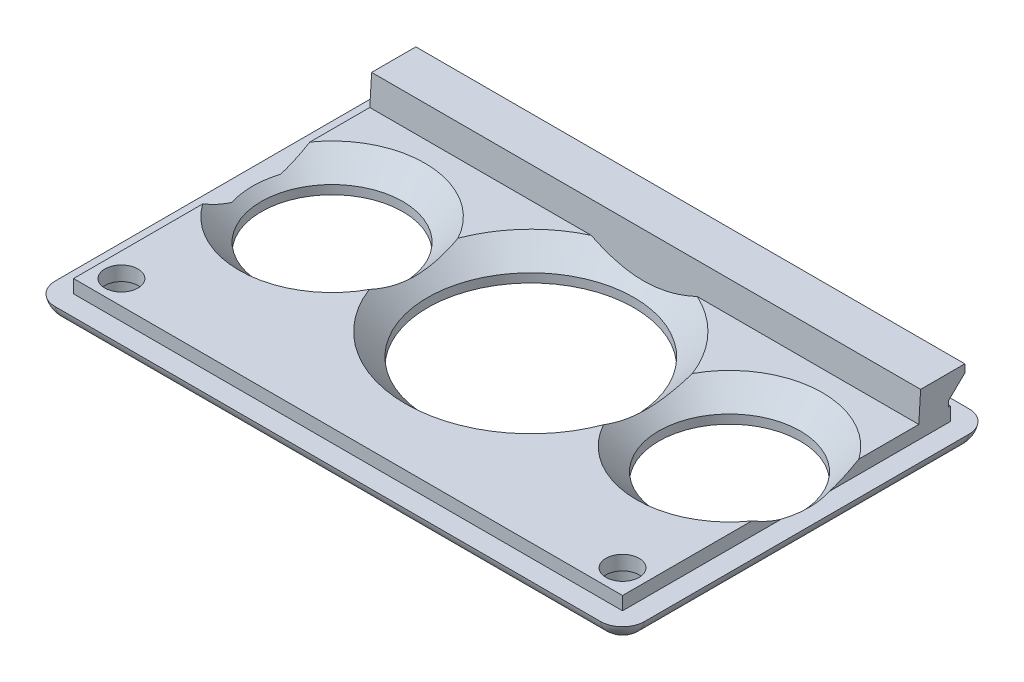
SolidWorks part; units mm, degrees
ref_plane "Front Plane" through (0, 0, 0) normal (0, 0, 1) x (1, 0, 0)
ref_plane "Top Plane" through (0, 0, 0) normal (0, 1, 0) x (1, 0, 0)
ref_plane "Right Plane" through (0, 0, 0) normal (1, 0, 0) x (0, 0, -1)
sketch "Sketch1" plane through (0, 0, 0) normal (0, 1, 0) x (1, 0, 0)
  line L1 (-1.2463, 1.173) -> (78.7537, 1.173)
  line L2 (-1.2463, 1.173) -> (-1.2463, 51.173)
  line L3 (-1.2463, 51.173) -> (78.7537, 51.173)
  line L4 (78.7537, 1.173) -> (78.7537, 51.173)
  dimension "D1" = 50
  dimension "D2" = 80
extrude "Boss-Extrude1" add sketch "Sketch1" along normal blind 2.4
sketch "Sketch2" plane through (0, 2.4, 0) normal (0, 1, 0) x (1, 0, 0)
  line L0 (38.7537, 51.173) -> (38.7537, 1.173) construction
  line L1 (78.7537, 51.173) -> (-1.2463, 51.173) construction
  line L2 (-1.2463, 1.173) -> (78.7537, 1.173) construction
  line L3 (-1.2463, 51.173) -> (-1.2463, 1.173) construction
  line L4 (1.5037, 48.423) -> (76.0037, 48.423)
  line L5 (1.5037, 48.423) -> (1.5037, 3.923)
  line L6 (1.5037, 3.923) -> (76.0037, 3.923)
  line L7 (76.0037, 48.423) -> (76.0037, 3.923)
  line L8 (1.5037, 48.423) -> (76.0037, 3.923) construction
  line L9 (1.5037, 3.923) -> (76.0037, 48.423) construction
  point P6 (38.7537, 26.173)
  dimension "D1" = 2.75
  dimension "D2" = 2.75
extrude "Boss-Extrude2" add sketch "Sketch2" along normal blind 1.8
sketch "Sketch3" [suppressed] plane through (0, 0, 0) normal (0, -1, 0) x (-1, 0, 0)
  line L1 (-74.0007, 57.8979) -> (-74.348, 7.8991) construction
  line L2 (-74.348, 7.8991) -> (0.6502, 7.3782) construction
  line L3 (0.6502, 7.3782) -> (0.9975, 57.377) construction
  line L4 (0.9975, 57.377) -> (-74.0007, 57.8979) construction
  circle A0 centre (-61.0257, 35.0904) radius 9.305
  circle A1 centre (-36.6576, 35.188) radius 13.2617
  circle A2 centre (-12.0957, 35.0904) radius 9.305
  circle A3 centre (-67.6316, 45.7049) radius 3.1
  circle A4 centre (-18.7016, 45.7049) radius 3.1
  circle A5 centre (-68.3065, 13.8573) radius 1.75
  circle A6 centre (-5.3158, 13.4277) radius 1.75
sketch "Sketch4" plane through (0, 0, 0) normal (0, -1, 0) x (-1, 0, 0)
  line L0 (-78.7537, 55.2723) -> (-78.7537, 28.723) construction
  line L1 (1.2463, 1.173) -> (-78.7537, 1.173) construction
  line L2 (-65.7187, 28.723) -> (-38.7537, 28.723) construction
  line L3 (-38.7537, 28.723) -> (-11.7887, 28.723) construction
  line L4 (-65.7187, 28.723) -> (-78.7537, 28.723) construction
  line L5 (-4.7537, 7.173) -> (-72.7537, 7.173) construction
  line L6 (-72.7537, 7.173) -> (-73.7537, 7.173) construction
  line L7 (-73.7537, 7.173) -> (-72.7537, 7.173) construction
  line L8 (-72.7537, 7.173) -> (-72.7537, 4.923) construction
  line L9 (-72.7537, 4.923) -> (-72.7537, 7.173) construction
  line L10 (-72.7537, 7.173) -> (-72.7537, 9.423) construction
  line L11 (-11.7887, 28.723) -> (-28.1542, 28.723) construction
  line L13 (-4.7537, 7.173) -> (-4.7537, 1.1651) construction
  line L14 (-4.7537, 1.1651) -> (-4.7537, 7.173) construction
  line L15 (-4.7537, 7.173) -> (-4.7537, 9.423) construction
  line L16 (-78.7537, 1.173) -> (-78.7537, 51.173) construction
  line L17 (-38.7537, 28.723) -> (-38.7537, 51.173) construction
  line L18 (-78.7537, 51.173) -> (1.2463, 51.173) construction
  line L19 (1.2463, 51.173) -> (1.2463, 1.173) construction
  circle A0 centre (-65.7187, 28.723) radius 9.6
  circle A1 centre (-38.7537, 28.723) radius 14
  circle A2 centre (-11.7887, 28.723) radius 9.6
  circle A3 centre (-72.7537, 7.173) radius 2.25
  circle A4 centre (-4.7537, 7.173) radius 2.25
  dimension "D5" = 28
  dimension "D6" = 19.2
  dimension "D7" = 4.5
  dimension "D3" = 26.965
  dimension "D4" = 26.965
  dimension "D8" = 6
  dimension "D2" = 6
  dimension "D1" = 6
extrude "Cut-Extrude1" cut sketch "Sketch4" against normal through all
sketch "Sketch5" plane through (76.0037, 0, 0) normal (1, 0, 0) x (0, 0, -1)
  line L0 (48.123, 4.2) -> (44.123, 4.2)
  line L1 (3.923, 4.2) -> (48.423, 4.2) construction
  line L2 (44.123, 4.2) -> (44.373, 8.2)
  line L3 (44.373, 8.2) -> (50.373, 8.2)
  line L4 (50.373, 8.2) -> (50.373, 7.1)
  line L6 (48.1425, 4.9783) -> (48.123, 4.2)
  line L7 (48.423, 4.2) -> (48.423, 2.4) construction
  line L8 (51.173, 2.4) -> (51.173, 0) construction
  line L9 (48.1425, 4.9783) -> (50.373, 7.1)
  dimension "D1" = 1.1
  dimension "D2" = 4
  dimension "D3" = 0.3
  dimension "D4" = 0.8
  dimension "D5" = 4
  dimension "D6" = 6
  dimension "D8" = 135
extrude "Boss-Extrude3" add sketch "Sketch5" against normal up to surface (74.5 mm away) up to face at (1.5037, 3.3, -26.173)
sketch "Sketch6" plane through (0, 0, 0) normal (0, -1, 0) x (1, 0, 0)
  line L0 (72.3246, -42.4375) -> (72.3246, -36.2375) construction
  line L1 (78.7537, -1.173) -> (78.7537, -51.173) construction
  line L3 (78.7537, -51.173) -> (-1.2463, -51.173) construction
  line L4 (-1.2463, -51.173) -> (-1.2463, -1.173) construction
  circle A0 centre (72.3246, -39.3375) radius 3.65
  circle A1 centre (18.3946, -39.3375) radius 3.65
  dimension "D1" = 7.3
  dimension "D2" = 6.429
  dimension "D3" = 11.8356
  dimension "D4" = 19.641
  dimension "D5" = 11.8356
extrude "Cut-Extrude2" [suppressed] cut sketch "Sketch6" against normal through all
fillet "Fillet1" radius 3 4 edges at (-1.2463, 1.2, -51.173) (-1.2463, 1.2, -1.173) (78.7537, 1.2, -1.173) (78.7537, 1.2, -51.173)
fillet "Fillet2" radius 3 8 edges at (-0.3677, 0, -50.2943) (38.7537, 0, -51.173) (77.875, 0, -50.2943) (78.7537, 0, -26.173) (77.875, 0, -2.0517) (38.7537, 0, -1.173) (-0.3677, 0, -2.0517) (-1.2463, 0, -26.173)
sketch "Sketch7" plane through (0, 0, 0) normal (0, -1, 0) x (1, 0, 0)
  circle A0 centre (4.7537, -7.173) radius 3
  circle A1 centre (72.7537, -7.173) radius 3
  dimension "D1" = 6
extrude "Cut-Extrude3" cut sketch "Sketch7" against normal blind 2.25
chamfer "Chamfer1" distance 3 angle 45 3 edges at (65.7187, 4.2, -38.323) (38.7537, 4.2, -42.723) (11.7887, 4.2, -38.323)
equation "\"ir distance\"=26.965"
equation "\"D3@Sketch4\"=\"ir distance\""
equation "\"D4@Sketch4\"=\"ir distance\""
